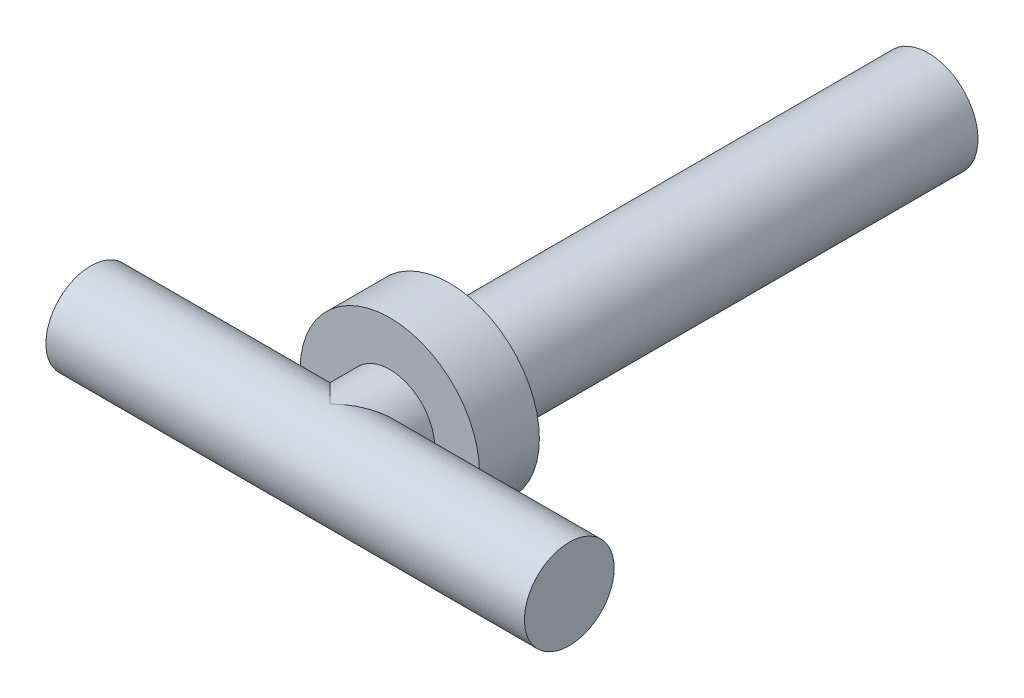
SolidWorks part; units mm, degrees
material "AISI 316 Annealed Stainless Steel Bar (SS)"
ref_plane "Front Plane" through (0, 0, 0) normal (0, 0, 1) x (1, 0, 0)
ref_plane "Top Plane" through (0, 0, 0) normal (0, 1, 0) x (1, 0, 0)
ref_plane "Right Plane" through (0, 0, 0) normal (1, 0, 0) x (0, 0, -1)
sketch "Extrude sketch 1" plane through (0, 0, 0) normal (0, 0, 1) x (1, 0, 0)
  circle A0 centre (0, 0) radius 5
  dimension "D1" = 10
extrude "Extrude 1" add sketch "Extrude sketch 1" along normal blind 52 from offset 22 separate body offset against normal yes
sketch "Extrude sketch 2" plane through (0, 0, 0) normal (0, 0, 1) x (1, 0, 0)
  circle A0 centre (0, 0) radius 9
  dimension "D1" = 18
extrude "Extrude 2" add sketch "Extrude sketch 2" along normal blind 6 from offset 26 separate body
sketch "Pipe sketch 1" plane through (0, 0, 0) normal (0, 0, 1) x (1, 0, 0)
  circle A0 centre (0, 0) radius 4.5
  dimension "D1" = 9
extrude "Pipe 1" add sketch "Pipe sketch 1" along normal blind 48 separate body
move or copy body "Pipe rotate 1" bodies to move or copy 103 copy no rotation origin (0, 0, 0) rotation axis (0, 1, 0) rotation angle 90
move or copy body "Pipe place 1" bodies to move or copy 104 copy no translate (-24, 0, 38) parameters "D1"=24, "D2"=0, "D3"=38
sketch "Extrude sketch 3" plane through (0, 0, 0) normal (0, 0, 1) x (1, 0, 0)
  circle A0 centre (0, 0) radius 4.5
  dimension "D1" = 9
extrude "Extrude 3" add sketch "Extrude sketch 3" along normal blind 8 from offset 30 separate body
combine bodies "Combine (weld / assembly of features)" operation type add bodies to combine 105 102 106 101
